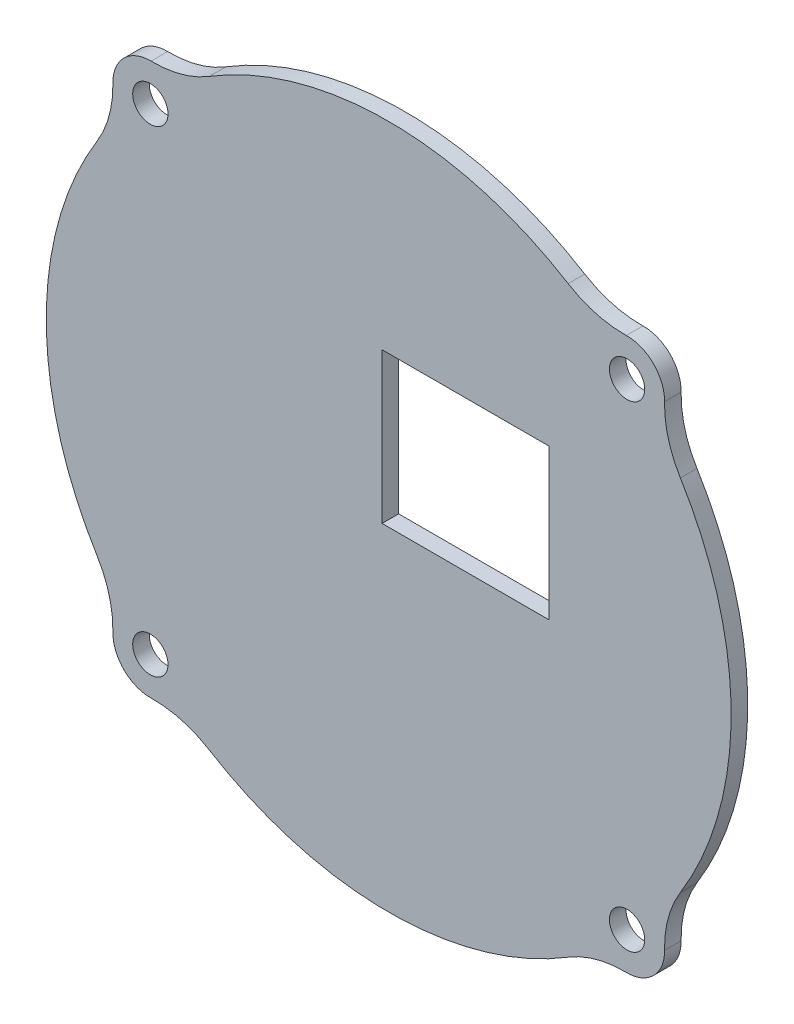
SolidWorks part; units mm, degrees
ref_plane "Plan de face" through (0, 0, 0) normal (0, 0, 1) x (1, 0, 0)
ref_plane "Plan de dessus" through (0, 0, 0) normal (0, 1, 0) x (1, 0, 0)
ref_plane "Plan de droite" through (0, 0, 0) normal (1, 0, 0) x (0, 0, -1)
sketch "Esquisse1" plane through (0, 0, 0) normal (0, 0, 1) x (1, 0, 0)
  line L0 (0, 31.5) -> (0, 0) construction
  line L1 (15.5, 21) -> (-15.5, 21) construction
  line L2 (15.5, 21) -> (15.5, -21) construction
  line L3 (15.5, -21) -> (-15.5, -21) construction
  line L4 (-15.5, 21) -> (-15.5, -21) construction
  line L5 (15.5, 21) -> (-15.5, -21) construction
  line L6 (15.5, -21) -> (-15.5, 21) construction
  line L7 (0, 0) -> (-22.2739, 22.2739) construction
  arc A0 (-24.9579, 20.0276) -> (-24.9579, -20.0276) centre (0, 0) ccw
  circle A1 centre (0, 0) radius 31.5 construction
  circle A2 centre (-22.2739, 22.2739) radius 1.65
  circle A3 centre (22.2739, 22.2739) radius 1.65
  circle A4 centre (22.2739, -22.2739) radius 1.65
  circle A5 centre (-22.2739, -22.2739) radius 1.65
  arc A6 (-20.0276, 24.9579) -> (-24.9579, 20.0276) centre (-22.2739, 22.2739) ccw
  arc A7 (24.9579, 20.0276) -> (20.0276, 24.9579) centre (22.2739, 22.2739) ccw
  arc A8 (20.0276, -24.9579) -> (24.9579, -20.0276) centre (22.2739, -22.2739) ccw
  arc A9 (-24.9579, -20.0276) -> (-20.0276, -24.9579) centre (-22.2739, -22.2739) ccw
  arc A10 (20.0276, 24.9579) -> (-20.0276, 24.9579) centre (0, 0) ccw
  arc A11 (24.9579, -20.0276) -> (24.9579, 20.0276) centre (0, 0) ccw
  arc A13 (-20.0276, -24.9579) -> (20.0276, -24.9579) centre (0, 0) ccw
  point P0 (0, 0)
  point P21 (0, 0)
  point P29 (0, 0)
  dimension "D3" = 63
  dimension "D5" = 3.3
  dimension "D7" = 64
  dimension "D9" = 7
  dimension "D1" = 31
  dimension "D2" = 42
  dimension "D4" = 45
  dimension "D6" = 4
  dimension "D8" = 4
extrude "Boss.-Extru.1" add sketch "Esquisse1" along normal blind 1.55
sketch "Esquisse2" plane through (0, 0, 1.55) normal (0, 0, 1) x (1, 0, 0)
  line L1 (15, 20.5) -> (-15, 20.5) construction
  line L2 (15, 20.5) -> (15, -20.5) construction
  line L3 (15, -20.5) -> (-15, -20.5) construction
  line L4 (-15, 20.5) -> (-15, -20.5) construction
  line L5 (15, 20.5) -> (-15, -20.5) construction
  line L6 (15, -20.5) -> (-15, 20.5) construction
  point P0 (0, 0)
  dimension "D1" = 30
  dimension "D2" = 41
fillet "Congé1" radius 10 8 edges at (24.9579, -20.0276, 0.775) (20.0276, -24.9579, 0.775) (-20.0276, -24.9579, 0.775) (-24.9579, -20.0276, 0.775) (-24.9579, 20.0276, 0.775) (-20.0276, 24.9579, 0.775) (20.0276, 24.9579, 0.775) (24.9579, 20.0276, 0.775)
sketch "Esquisse3" plane through (0, 0, 1.55) normal (0, 0, 1) x (1, 0, 0)
  line L0 (15, 20.5) -> (15, -20.5) construction
  line L1 (15, 13.2085) -> (-0.6195, 13.2085)
  line L2 (15, 13.2085) -> (15, -0.8466)
  line L3 (15, -0.8466) -> (-0.6195, -0.8466)
  line L4 (-0.6195, 13.2085) -> (-0.6195, -0.8466)
  line L5 (15, 20.5) -> (-15, -20.5) construction
extrude "Enlèv. mat.-Extru.1" cut sketch "Esquisse3" against normal through all
